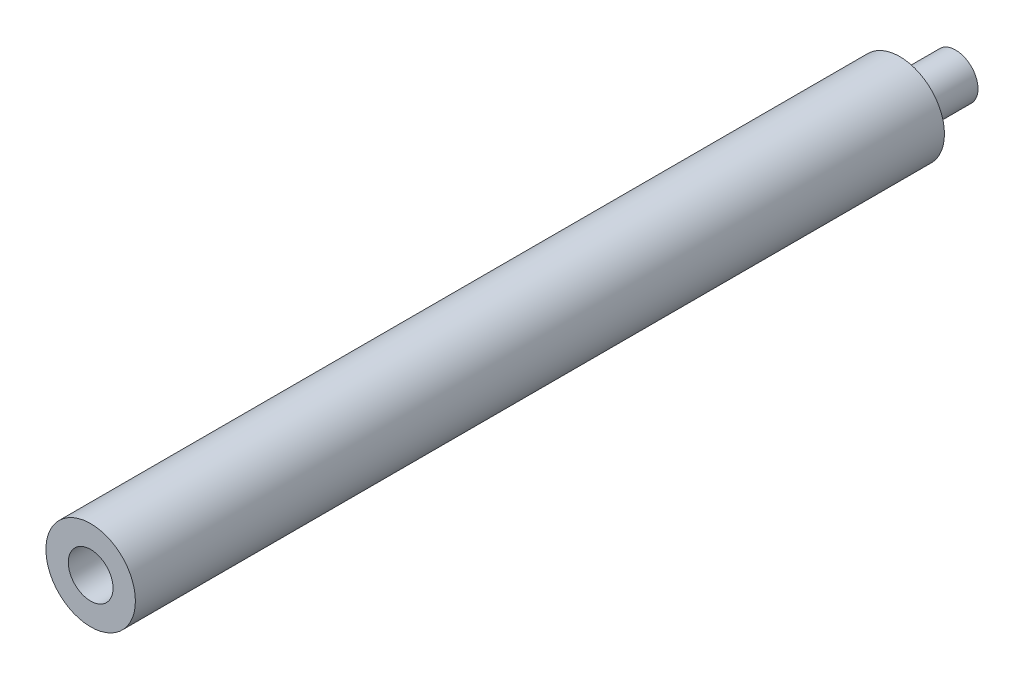
SolidWorks part; units mm, degrees
ref_plane "Front Plane" through (0, 0, 0) normal (0, 0, 1) x (1, 0, 0)
ref_plane "Top Plane" through (0, 0, 0) normal (0, 1, 0) x (1, 0, 0)
ref_plane "Right Plane" through (0, 0, 0) normal (1, 0, 0) x (0, 0, -1)
sketch "Sketch1" plane through (0, 0, 0) normal (0, 0, 1) x (1, 0, 0)
  circle A0 centre (0, 0) radius 6
  dimension "D1" = 12
extrude "Boss-Extrude1" add sketch "Sketch1" along normal mid plane 108.5
sketch "Sketch2" plane through (0, 0, 54.25) normal (0, 0, 1) x (1, 0, 0)
  circle A0 centre (0, 0) radius 3
  dimension "D1" = 6
sketch "Sketch3" plane through (0, 0, -54.25) normal (0, 0, -1) x (-1, 0, 0)
  circle A0 centre (0, 0) radius 3
  dimension "D1" = 6
extrude "Boss-Extrude3" add sketch "Sketch3" along normal blind 7.5
extrude "Cut-Extrude1" cut sketch "Sketch2" against normal blind 5
